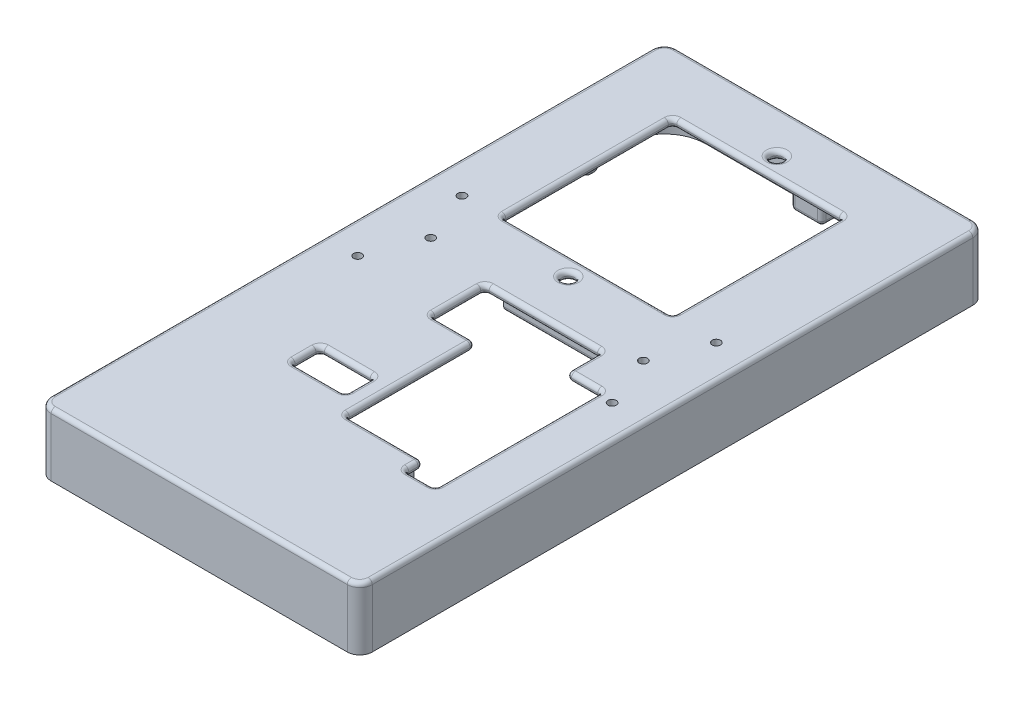
SolidWorks part; units mm, degrees
ref_plane "前视基准面" through (0, 0, 0) normal (0, 0, 1) x (1, 0, 0)
ref_plane "上视基准面" through (0, 0, 0) normal (0, 1, 0) x (1, 0, 0)
ref_plane "右视基准面" through (0, 0, 0) normal (1, 0, 0) x (0, 0, -1)
sketch "草图1" plane through (0, 0, 0) normal (0, 1, 0) x (1, 0, 0)
  line L0 (-212.3169, 718.1207) -> (-234.7066, 815.582) construction
  line L1 (-132.5632, 1387.3532) -> (-132.5632, 1244.1403) construction
  line L2 (-45.1474, 1386.0064) -> (-45.1474, 1242.0064)
  line L3 (-110.6474, 1387.5064) -> (-86.8035, 1387.5064)
  line L4 (-120.6474, 1377.5064) -> (-120.6474, 1369.0064)
  line L5 (-110.6474, 1240.5064) -> (-86.8035, 1240.5064)
  line L6 (-46.6474, 1377.5064) -> (-46.6474, 1369.0064)
  line L7 (-119.1474, 1239.0064) -> (-48.1474, 1239.0064)
  line L8 (-122.1474, 1386.0064) -> (-122.1474, 1242.0064)
  line L9 (-119.1474, 1389.0064) -> (-48.1474, 1389.0064)
  line L10 (-120.6474, 1240.5064) -> (-46.6474, 1240.5064) construction
  line L11 (-46.6474, 1387.5064) -> (-46.6474, 1240.5064) construction
  line L12 (-120.6474, 1387.5064) -> (-120.6474, 1240.5064) construction
  line L13 (-120.6474, 1387.5064) -> (-46.6474, 1387.5064) construction
  line L14 (-45.1474, 1389.0064) -> (-45.1474, 1239.0064) construction
  line L15 (-122.1474, 1239.0064) -> (-45.1474, 1239.0064) construction
  line L16 (-122.1474, 1389.0064) -> (-122.1474, 1239.0064) construction
  line L17 (-122.1474, 1389.0064) -> (-45.1474, 1389.0064) construction
  line L18 (-83.6474, 1387.5064) -> (-83.6474, 1240.5064) construction
  line L19 (-46.6474, 1369.0064) -> (-49.6474, 1369.0064)
  line L21 (-46.6474, 1366.0064) -> (-49.6474, 1366.0064)
  line L22 (-49.6474, 1369.0064) -> (-49.6474, 1366.0064)
  line L23 (-46.6474, 1314.0064) -> (-120.6474, 1314.0064) construction
  line L24 (-46.6474, 1366.0064) -> (-46.6474, 1262.0064)
  line L25 (-46.6474, 1259.0064) -> (-49.6474, 1259.0064)
  line L26 (-49.6474, 1259.0064) -> (-49.6474, 1262.0064)
  line L27 (-46.6474, 1262.0064) -> (-49.6474, 1262.0064)
  line L28 (-120.6474, 1369.0064) -> (-117.6474, 1369.0064)
  line L29 (-117.6474, 1369.0064) -> (-117.6474, 1366.0064)
  line L30 (-120.6474, 1366.0064) -> (-117.6474, 1366.0064)
  line L31 (-120.6474, 1262.0064) -> (-117.6474, 1262.0064)
  line L32 (-117.6474, 1259.0064) -> (-117.6474, 1262.0064)
  line L33 (-46.6474, 1259.0064) -> (-46.6474, 1250.5064)
  line L34 (-120.6474, 1366.0064) -> (-120.6474, 1262.0064)
  line L35 (-117.6474, 1259.0064) -> (-120.6474, 1259.0064)
  line L36 (-120.6474, 1259.0064) -> (-120.6474, 1250.5064)
  line L37 (-79.37, 1387.5064) -> (-56.6474, 1387.5064)
  line L39 (-79.37, 1387.5064) -> (-79.37, 1384.0064)
  line L40 (-79.37, 1384.0064) -> (-86.8035, 1384.0064)
  line L41 (-86.8035, 1387.5064) -> (-86.8035, 1384.0064)
  line L43 (-80.7882, 1240.5064) -> (-80.7882, 1243.5064)
  line L44 (-80.7882, 1243.5064) -> (-86.8035, 1243.5064)
  line L45 (-86.8035, 1240.5064) -> (-86.8035, 1243.5064)
  line L46 (-80.7882, 1240.5064) -> (-56.6474, 1240.5064)
  arc A0 (-56.6474, 1240.5064) -> (-46.6474, 1250.5064) centre (-56.6474, 1250.5064) ccw
  arc A1 (-120.6474, 1250.5064) -> (-110.6474, 1240.5064) centre (-110.6474, 1250.5064) ccw
  arc A2 (-110.6474, 1387.5064) -> (-120.6474, 1377.5064) centre (-110.6474, 1377.5064) ccw
  arc A3 (-56.6474, 1387.5064) -> (-46.6474, 1377.5064) centre (-56.6474, 1377.5064) cw
  arc A4 (-45.1474, 1242.0064) -> (-48.1474, 1239.0064) centre (-48.1474, 1242.0064) cw
  arc A5 (-119.1474, 1239.0064) -> (-122.1474, 1242.0064) centre (-119.1474, 1242.0064) cw
  arc A6 (-122.1474, 1386.0064) -> (-119.1474, 1389.0064) centre (-119.1474, 1386.0064) cw
  arc A7 (-45.1474, 1386.0064) -> (-48.1474, 1389.0064) centre (-48.1474, 1386.0064) ccw
  point P48 (-48.1474, 1259.0064)
  point P55 (-119.1474, 1259.0064)
  dimension "D3" = 10
  dimension "D4" = 3
  dimension "D1" = 100
  dimension "D5" = 3
  dimension "D6" = 20
  dimension "D7" = 3
  dimension "D8" = 71
  dimension "D9" = 144
  dimension "D10" = 3.5
  dimension "D11" = 3
  dimension "D2" = 1.5
extrude "凸台-拉伸1" add sketch "草图1" along normal blind 15
fillet "圆角1" radius 1 12 edges at (-117.6474, 7.5, -1259.0064) (-117.6474, 7.5, -1262.0064) (-49.6474, 7.5, -1259.0064) (-49.6474, 7.5, -1262.0064) (-49.6474, 7.5, -1366.0064) (-49.6474, 7.5, -1369.0064) (-117.6474, 7.5, -1366.0064) (-117.6474, 7.5, -1369.0064) (-86.8035, 7.5, -1243.5064) (-80.7882, 7.5, -1243.5064) (-79.37, 7.5, -1384.0064) (-86.8035, 7.5, -1384.0064)
sketch "草图2" plane through (0, 15, 0) normal (0, 1, 0) x (1, 0, 0)
  line L0 (-117.9843, 1353.593) -> (-118.8671, 1253.5969) construction
  line L1 (-65.1474, 1308.7566) -> (-65.1474, 1318.5064)
  line L2 (-66.1474, 1319.5064) -> (-92.1474, 1319.5064)
  line L3 (-93.1474, 1318.5064) -> (-93.1474, 1313.0064)
  line L4 (-45.1474, 1242.0064) -> (-45.1474, 1386.0064)
  line L5 (-48.1474, 1389.0064) -> (-119.1474, 1389.0064)
  line L6 (-122.1474, 1386.0064) -> (-122.1474, 1242.0064)
  line L7 (-119.1474, 1239.0064) -> (-48.1474, 1239.0064)
  line L8 (-45.1474, 1242.0064) -> (-45.1474, 1386.0064)
  line L9 (-48.1474, 1389.0064) -> (-119.1474, 1389.0064)
  line L10 (-122.1474, 1386.0064) -> (-122.1474, 1242.0064)
  line L11 (-119.1474, 1239.0064) -> (-48.1474, 1239.0064)
  line L12 (-94.1474, 1312.0064) -> (-95.1474, 1312.0064)
  line L13 (-96.1474, 1311.0064) -> (-96.1474, 1305.0064)
  line L14 (-95.1474, 1304.0064) -> (-86.1474, 1304.0064)
  line L15 (-85.1474, 1303.0064) -> (-85.1474, 1274.0064)
  line L16 (-84.1474, 1273.0064) -> (-65.1474, 1273.0064)
  line L17 (-89.1474, 1277.5064) -> (-99.1474, 1277.5064)
  line L18 (-100.1474, 1278.5064) -> (-100.1474, 1283.5064)
  line L19 (-99.1474, 1284.5064) -> (-89.1474, 1284.5064)
  line L20 (-88.1474, 1283.5064) -> (-88.1474, 1278.5064)
  line L21 (-84.6474, 1378.5064) -> (-84.6474, 1328.5064) construction
  line L22 (-104.1474, 1374.0064) -> (-65.1474, 1374.0064)
  line L23 (-105.1474, 1373.0064) -> (-105.1474, 1334.0064)
  line L24 (-104.1474, 1333.0064) -> (-65.1474, 1333.0064)
  line L25 (-64.1474, 1373.0064) -> (-64.1474, 1334.0064)
  line L26 (-65.1474, 1273.0064) -> (-64.1474, 1273.0064)
  line L27 (-65.1474, 1308.7566) -> (-55.8177, 1308.7566)
  line L28 (-64.1474, 1273.0064) -> (-64.1474, 1269.7566)
  line L29 (-63.1474, 1268.7566) -> (-56.8177, 1268.7566)
  line L30 (-55.8177, 1308.7566) -> (-55.8177, 1269.7566)
  arc A0 (-65.1474, 1318.5064) -> (-66.1474, 1319.5064) centre (-66.1474, 1318.5064) ccw
  arc A2 (-85.1474, 1274.0064) -> (-84.1474, 1273.0064) centre (-84.1474, 1274.0064) ccw
  arc A3 (-86.1474, 1304.0064) -> (-85.1474, 1303.0064) centre (-86.1474, 1303.0064) cw
  arc A4 (-48.1474, 1239.0064) -> (-45.1474, 1242.0064) centre (-48.1474, 1242.0064) ccw
  arc A5 (-45.1474, 1386.0064) -> (-48.1474, 1389.0064) centre (-48.1474, 1386.0064) ccw
  arc A6 (-119.1474, 1389.0064) -> (-122.1474, 1386.0064) centre (-119.1474, 1386.0064) ccw
  arc A7 (-122.1474, 1242.0064) -> (-119.1474, 1239.0064) centre (-119.1474, 1242.0064) ccw
  arc A8 (-48.1474, 1239.0064) -> (-45.1474, 1242.0064) centre (-48.1474, 1242.0064) ccw
  arc A9 (-45.1474, 1386.0064) -> (-48.1474, 1389.0064) centre (-48.1474, 1386.0064) ccw
  arc A10 (-119.1474, 1389.0064) -> (-122.1474, 1386.0064) centre (-119.1474, 1386.0064) ccw
  arc A11 (-122.1474, 1242.0064) -> (-119.1474, 1239.0064) centre (-119.1474, 1242.0064) ccw
  arc A12 (-92.1474, 1319.5064) -> (-93.1474, 1318.5064) centre (-92.1474, 1318.5064) ccw
  arc A13 (-93.1474, 1313.0064) -> (-94.1474, 1312.0064) centre (-94.1474, 1313.0064) cw
  arc A14 (-95.1474, 1312.0064) -> (-96.1474, 1311.0064) centre (-95.1474, 1311.0064) ccw
  arc A15 (-96.1474, 1305.0064) -> (-95.1474, 1304.0064) centre (-95.1474, 1305.0064) ccw
  arc A16 (-89.1474, 1284.5064) -> (-88.1474, 1283.5064) centre (-89.1474, 1283.5064) cw
  arc A17 (-89.1474, 1277.5064) -> (-88.1474, 1278.5064) centre (-89.1474, 1278.5064) ccw
  arc A18 (-99.1474, 1277.5064) -> (-100.1474, 1278.5064) centre (-99.1474, 1278.5064) cw
  arc A19 (-100.1474, 1283.5064) -> (-99.1474, 1284.5064) centre (-99.1474, 1283.5064) cw
  arc A20 (-65.1474, 1333.0064) -> (-64.1474, 1334.0064) centre (-65.1474, 1334.0064) ccw
  arc A21 (-105.1474, 1334.0064) -> (-104.1474, 1333.0064) centre (-104.1474, 1334.0064) ccw
  arc A22 (-104.1474, 1374.0064) -> (-105.1474, 1373.0064) centre (-104.1474, 1373.0064) ccw
  arc A23 (-65.1474, 1374.0064) -> (-64.1474, 1373.0064) centre (-65.1474, 1373.0064) cw
  circle A24 centre (-84.6474, 1378.5064) radius 1.5
  circle A25 centre (-84.6474, 1328.5064) radius 1.5
  arc A26 (-64.1474, 1269.7566) -> (-63.1474, 1268.7566) centre (-63.1474, 1269.7566) ccw
  arc A27 (-56.8177, 1268.7566) -> (-55.8177, 1269.7566) centre (-56.8177, 1269.7566) ccw
  point P28 (-65.1474, 1319.5064)
  point P31 (-65.1474, 1273.0064)
  point P34 (-85.1474, 1273.0064)
  point P37 (-85.1474, 1304.0064)
  point P40 (-93.1474, 1319.5064)
  point P43 (-93.1474, 1312.0064)
  point P46 (-96.1474, 1312.0064)
  point P49 (-96.1474, 1304.0064)
  point P52 (-88.1474, 1284.5064)
  point P55 (-88.1474, 1277.5064)
  point P58 (-100.1474, 1277.5064)
  point P69 (-105.1474, 1333.0064)
  point P72 (-105.1474, 1374.0064)
  point P75 (-64.1474, 1374.0064)
  point P78 (-84.6474, 1353.5064)
  point P79 (-64.1474, 1353.5064)
  dimension "D15" = 1
  dimension "D20" = 1
  dimension "D22" = 34
  dimension "D23" = 1
  dimension "D2" = 100
  dimension "D3" = 20
  dimension "D4" = 28
  dimension "D5" = 7.5
  dimension "D6" = 8
  dimension "D7" = 11
  dimension "D8" = 3
  dimension "D9" = 31
  dimension "D10" = 39
  dimension "D11" = 46.5
  dimension "D12" = 22
  dimension "D13" = 12
  dimension "D14" = 7
  dimension "D16" = 19
  dimension "D17" = 15
  dimension "D18" = 41
  dimension "D19" = 41
  dimension "D21" = 50
  dimension "D24" = 38.5
  dimension "D1" = 0
extrude "凸台-拉伸2" add sketch "草图2" against normal blind 2
sketch "草图6" plane through (0, 15, 0) normal (0, 1, 0) x (1, 0, 0)
  line L0 (-93.1474, 1313.0064) -> (-93.1474, 1304.0064)
  line L1 (-95.1474, 1304.0064) -> (-86.1474, 1304.0064) construction
  line L2 (-93.1474, 1304.0064) -> (-97.2959, 1304.0064)
  line L3 (-97.2959, 1304.0064) -> (-97.2959, 1313.0064)
  line L4 (-97.2959, 1313.0064) -> (-93.1474, 1313.0064)
  line L5 (-56.8177, 1268.7566) -> (-56.8177, 1308.7566)
  line L6 (-55.8177, 1308.7566) -> (-65.1474, 1308.7566) construction
  line L7 (-56.8177, 1308.7566) -> (-55.8177, 1308.7566)
  line L8 (-55.8177, 1308.7566) -> (-55.8177, 1268.7566)
  line L9 (-55.8177, 1268.7566) -> (-56.8177, 1268.7566)
  line L10 (-93.1474, 1317.0064) -> (-65.1474, 1317.0064)
  line L11 (-93.1474, 1318.5064) -> (-93.1474, 1313.0064) construction
  line L12 (-65.1474, 1308.7566) -> (-65.1474, 1318.5064) construction
  line L13 (-66.1474, 1319.5064) -> (-92.1474, 1319.5064) construction
  line L14 (-93.1474, 1317.0064) -> (-93.1474, 1319.5064)
  line L15 (-93.1474, 1319.5064) -> (-65.1474, 1319.5064)
  line L16 (-65.1474, 1319.5064) -> (-65.1474, 1317.0064)
  line L17 (-82.6474, 1273.0064) -> (-82.6474, 1304.0064)
  line L18 (-84.1474, 1273.0064) -> (-64.1474, 1273.0064) construction
  line L19 (-82.6474, 1304.0064) -> (-86.6707, 1304.0064)
  line L20 (-85.1474, 1303.0064) -> (-85.1474, 1274.0064) construction
  line L21 (-82.6474, 1273.0064) -> (-86.6707, 1273.0064)
  line L22 (-86.6707, 1273.0064) -> (-86.6707, 1304.0064)
  dimension "D1" = 2.5
  dimension "D2" = 2.5
extrude "凸台-拉伸4" add sketch "草图6" against normal up to surface (2 mm away) up to face at (-83.5912, 13, -1313.9609)
fillet "圆角7" radius 1 9 edges at (-93.1474, 14, -1317.0064) (-93.1474, 14, -1304.0064) (-82.6474, 14, -1304.0064) (-82.6474, 14, -1273.0064) (-64.1474, 14, -1273.0064) (-56.8177, 14, -1268.7566) (-56.8177, 14, -1308.7566) (-65.1474, 14, -1308.7566) (-65.1474, 14, -1317.0064)
sketch "草图7" plane through (0, 15, 0) normal (0, 1, 0) x (1, 0, 0)
  line L0 (-89.1474, 1284.5064) -> (-88.1474, 1284.5064)
  line L1 (-87.1474, 1283.5064) -> (-87.1474, 1278.5064)
  line L2 (-88.1474, 1277.5064) -> (-89.1474, 1277.5064)
  line L3 (-89.1474, 1277.5064) -> (-89.1474, 1284.5064)
  arc A0 (-87.1474, 1278.5064) -> (-88.1474, 1277.5064) centre (-88.1474, 1278.5064) cw
  arc A1 (-88.1474, 1284.5064) -> (-87.1474, 1283.5064) centre (-88.1474, 1283.5064) cw
  dimension "D1" = 1
extrude "切除-拉伸3" cut sketch "草图7" against normal up to surface (2 mm away) up to face at (-72.3815, 13, -1294.3064)
sketch "草图8" plane through (0, 13, 0) normal (0, -1, 0) x (1, 0, 0)
  line L0 (-46.6474, -1314.0064) -> (-120.6474, -1314.0064) construction
  line L1 (-46.6474, -1262.0064) -> (-46.6474, -1366.0064) construction
  line L2 (-120.6474, -1366.0064) -> (-120.6474, -1262.0064) construction
  line L3 (-48.6474, -1369.0064) -> (-46.6474, -1369.0064) construction
  line L4 (-49.6474, -1367.0064) -> (-49.6474, -1368.0064) construction
  line L5 (-46.6474, -1366.0064) -> (-48.6474, -1366.0064) construction
  line L6 (-48.6474, -1369.0064) -> (-46.6474, -1369.0064) construction
  line L7 (-49.6474, -1367.0064) -> (-49.6474, -1368.0064) construction
  line L8 (-46.6474, -1366.0064) -> (-48.6474, -1366.0064) construction
  line L9 (-48.6474, -1315.5064) -> (-46.6474, -1315.5064)
  line L10 (-49.6474, -1313.5064) -> (-49.6474, -1314.5064)
  line L11 (-46.6474, -1312.5064) -> (-48.6474, -1312.5064)
  line L12 (-83.6474, -1389.0064) -> (-83.6474, -1239.0064) construction
  line L13 (-48.1474, -1389.0064) -> (-119.1474, -1389.0064) construction
  line L14 (-119.1474, -1239.0064) -> (-48.1474, -1239.0064) construction
  line L15 (-120.6474, -1312.5064) -> (-118.6474, -1312.5064)
  line L16 (-117.6474, -1313.5064) -> (-117.6474, -1314.5064)
  line L17 (-118.6474, -1315.5064) -> (-120.6474, -1315.5064)
  line L18 (-46.6474, -1315.5064) -> (-46.6474, -1312.5064)
  line L19 (-120.6474, -1315.5064) -> (-120.6474, -1312.5064)
  arc A0 (-49.6474, -1368.0064) -> (-48.6474, -1369.0064) centre (-48.6474, -1368.0064) ccw construction
  arc A1 (-48.6474, -1366.0064) -> (-49.6474, -1367.0064) centre (-48.6474, -1367.0064) ccw construction
  arc A2 (-49.6474, -1368.0064) -> (-48.6474, -1369.0064) centre (-48.6474, -1368.0064) ccw construction
  arc A3 (-48.6474, -1366.0064) -> (-49.6474, -1367.0064) centre (-48.6474, -1367.0064) ccw construction
  arc A4 (-49.6474, -1314.5064) -> (-48.6474, -1315.5064) centre (-48.6474, -1314.5064) ccw
  arc A5 (-48.6474, -1312.5064) -> (-49.6474, -1313.5064) centre (-48.6474, -1313.5064) ccw
  arc A6 (-118.6474, -1312.5064) -> (-117.6474, -1313.5064) centre (-118.6474, -1313.5064) cw
  arc A7 (-117.6474, -1314.5064) -> (-118.6474, -1315.5064) centre (-118.6474, -1314.5064) cw
  dimension "D1" = 2
extrude "凸台-拉伸5" add sketch "草图8" along normal up to surface (13 mm away) up to face at (-83.6474, 0, -1314.0064)
fillet "圆角2" radius 1 46 edges at (-93.1474, 15, -1310.5064) (-87.8974, 15, -1304.0064) (-73.3974, 15, -1273.0064) (-65.1474, 15, -1312.8815) (-93.6474, 15, -1284.5064) (-99.8545, 15, -1284.2135) (-100.1474, 15, -1281.0064) (-99.8545, 15, -1277.7993) (-93.6474, 15, -1277.5064) (-83.6474, 15, -1239.0064) (-121.2687, 15, -1239.885) (-122.1474, 15, -1314.0064) (-121.2687, 15, -1388.1277) (-83.6474, 15, -1389.0064) (-46.0261, 15, -1388.1277) (-45.1474, 15, -1314.0064) (-46.0261, 15, -1239.885) (-64.1474, 15, -1353.5064) (-64.4403, 15, -1373.7135) (-84.6474, 15, -1374.0064) (-104.8545, 15, -1373.7135) (-105.1474, 15, -1353.5064) (-104.8545, 15, -1333.2993) (-84.6474, 15, -1333.0064) (-64.4403, 15, -1333.2993) (-84.6474, 15, -1377.0064) (-84.6474, 15, -1327.0064) (-60.4826, 15, -1268.7566) (-60.9826, 15, -1308.7566) (-64.1474, 15, -1270.8815) (-63.8545, 15, -1269.0495) (-56.8177, 15, -1288.7566) (-79.1474, 15, -1317.0064) (-82.6474, 15, -1288.5064) (-87.4403, 15, -1277.7993) (-87.1474, 15, -1281.0064) (-87.4403, 15, -1284.2135) (-82.3545, 15, -1273.2993) (-64.4403, 15, -1272.7135) (-57.1106, 15, -1269.0495) (-57.1106, 15, -1308.4637) (-64.8545, 15, -1309.0495) (-65.4403, 15, -1316.7135) (-92.8545, 15, -1316.7135) (-92.8545, 15, -1304.2993) (-82.9403, 15, -1303.7135)
fillet "圆角3" radius 1 25 edges at (-49.3545, 0, -1261.7135) (-47.6474, 0, -1262.0064) (-49.6474, 0, -1260.5064) (-49.3545, 0, -1259.2993) (-47.6474, 0, -1259.0064) (-119.6474, 0, -1262.0064) (-117.9403, 0, -1261.7135) (-117.6474, 0, -1260.5064) (-117.9403, 0, -1259.2993) (-119.6474, 0, -1369.0064) (-117.9403, 0, -1368.7135) (-117.6474, 0, -1367.5064) (-117.9403, 0, -1366.2993) (-86.8035, 0, -1386.2564) (-86.5106, 0, -1384.2993) (-83.0867, 0, -1384.0064) (-79.6629, 0, -1384.2993) (-47.6474, 0, -1369.0064) (-49.3545, 0, -1368.7135) (-49.6474, 0, -1367.5064) (-49.3545, 0, -1366.2993) (-119.6474, 0, -1259.0064) (-119.6474, 0, -1366.0064) (-79.37, 0, -1386.2564) (-47.6474, 0, -1366.0064)
fillet "圆角4" radius 1 94 edges at (-73.3974, 13, -1273.0064) (-87.8974, 13, -1304.0064) (-93.1474, 13, -1310.5064) (-65.1474, 13, -1312.8815) (-93.6474, 13, -1277.5064) (-99.8545, 13, -1277.7993) (-100.1474, 13, -1281.0064) (-99.8545, 13, -1284.2135) (-93.6474, 13, -1284.5064) (-86.5106, 13, -1243.2135) (-83.7958, 13, -1243.5064) (-81.0811, 13, -1243.2135) (-80.7882, 13, -1241.5064) (-68.7178, 13, -1240.5064) (-49.5764, 13, -1243.4353) (-46.6474, 13, -1254.7564) (-47.6474, 13, -1259.0064) (-49.3545, 13, -1259.2993) (-49.6474, 13, -1260.5064) (-49.3545, 13, -1261.7135) (-47.6474, 13, -1262.0064) (-46.6474, 13, -1340.7564) (-46.6474, 13, -1287.2564) (-47.6474, 13, -1366.0064) (-49.3545, 13, -1366.2993) (-49.6474, 13, -1367.5064) (-49.3545, 13, -1368.7135) (-47.6474, 13, -1369.0064) (-46.6474, 13, -1373.2564) (-49.5764, 13, -1384.5774) (-68.0087, 13, -1387.5064) (-79.37, 13, -1386.2564) (-79.6629, 13, -1384.2993) (-83.0867, 13, -1384.0064) (-86.5106, 13, -1384.2993) (-86.8035, 13, -1386.2564) (-98.7254, 13, -1387.5064) (-117.7185, 13, -1384.5774) (-120.6474, 13, -1373.2564) (-119.6474, 13, -1369.0064) (-117.9403, 13, -1368.7135) (-117.6474, 13, -1367.5064) (-117.9403, 13, -1366.2993) (-119.6474, 13, -1366.0064) (-120.6474, 13, -1340.7564) (-120.6474, 13, -1287.2564) (-119.6474, 13, -1262.0064) (-117.9403, 13, -1261.7135) (-117.6474, 13, -1260.5064) (-117.9403, 13, -1259.2993) (-119.6474, 13, -1259.0064) (-120.6474, 13, -1254.7564) (-117.7185, 13, -1243.4353) (-98.7254, 13, -1240.5064) (-86.8035, 13, -1241.5064) (-104.8545, 13, -1333.2993) (-105.1474, 13, -1353.5064) (-104.8545, 13, -1373.7135) (-84.6474, 13, -1374.0064) (-64.4403, 13, -1373.7135) (-64.1474, 13, -1353.5064) (-64.4403, 13, -1333.2993) (-84.6474, 13, -1333.0064) (-84.6474, 13, -1377.0064) (-84.6474, 13, -1327.0064) (-60.9826, 13, -1308.7566) (-60.4826, 13, -1268.7566) (-63.8545, 13, -1269.0495) (-64.1474, 13, -1270.8815) (-82.6474, 13, -1288.5064) (-79.1474, 13, -1317.0064) (-56.8177, 13, -1288.7566) (-87.1474, 13, -1281.0064) (-87.4403, 13, -1277.7993) (-87.4403, 13, -1284.2135) (-92.8545, 13, -1304.2993) (-92.8545, 13, -1316.7135) (-65.4403, 13, -1316.7135) (-64.8545, 13, -1309.0495) (-57.1106, 13, -1308.4637) (-57.1106, 13, -1269.0495) (-64.4403, 13, -1272.7135) (-82.3545, 13, -1273.2993) (-82.9403, 13, -1303.7135) (-47.6474, 13, -1312.5064) (-49.3545, 13, -1312.7993) (-49.6474, 13, -1314.0064) (-49.3545, 13, -1315.2135) (-47.6474, 13, -1315.5064) (-119.6474, 13, -1315.5064) (-117.9403, 13, -1315.2135) (-117.6474, 13, -1314.0064) (-117.9403, 13, -1312.7993) (-119.6474, 13, -1312.5064)
sketch "草图3" plane through (0, 0, 0) normal (0, -1, 0) x (1, 0, 0)
  line L0 (-119.1474, -1239.0064) -> (-48.1474, -1239.0064) construction
  line L2 (-45.1474, -1242.0064) -> (-45.1474, -1386.0064) construction
  line L3 (-45.1474, -1314.0064) -> (-122.1474, -1314.0064) construction
  line L4 (-122.1474, -1386.0064) -> (-122.1474, -1242.0064) construction
  line L5 (-83.6474, -1314.0064) -> (-83.6474, -1389.0064) construction
  line L6 (-48.1474, -1389.0064) -> (-119.1474, -1389.0064) construction
  circle A0 centre (-47.6474, -1241.5064) radius 0.95
  circle A1 centre (-47.6474, -1386.5064) radius 0.95
  circle A2 centre (-119.6474, -1386.5064) radius 0.95
  circle A3 centre (-119.6474, -1241.5064) radius 0.95
  dimension "D2" = 1.9
  dimension "D3" = 2.5
  dimension "D1" = 2.5
extrude "切除-拉伸1" cut sketch "草图3" against normal blind 10
sketch "草图4" plane through (0, 13, 0) normal (0, -1, 0) x (1, 0, 0)
  line L5 (-65.1474, -1272.0064) -> (-84.1897, -1272.0064)
  line L6 (-65.1474, -1272.0064) -> (-65.1474, -1269.3636)
  line L7 (-92.1474, -1320.5064) -> (-66.0382, -1320.5064)
  line L8 (-92.1474, -1320.5064) -> (-92.1474, -1323.5064)
  line L9 (-91.1474, -1324.5064) -> (-67.0382, -1324.5064)
  line L10 (-66.0382, -1320.5064) -> (-66.0382, -1323.5064)
  line L11 (-65.1474, -1269.3636) -> (-83.1897, -1269.3636)
  line L12 (-84.1897, -1272.0064) -> (-84.1897, -1270.3636)
  line L13 (-108.4861, -1336.7616) -> (-111.7983, -1336.7616)
  line L14 (-107.4861, -1335.7616) -> (-107.4861, -1333.7616)
  line L15 (-108.4861, -1332.7616) -> (-111.7983, -1332.7616)
  line L16 (-112.7983, -1335.7616) -> (-112.7983, -1333.7616)
  arc A4 (-92.1474, -1323.5064) -> (-91.1474, -1324.5064) centre (-91.1474, -1323.5064) ccw
  arc A5 (-67.0382, -1324.5064) -> (-66.0382, -1323.5064) centre (-67.0382, -1323.5064) ccw
  arc A6 (-83.1897, -1269.3636) -> (-84.1897, -1270.3636) centre (-83.1897, -1270.3636) ccw
  arc A7 (-111.7983, -1332.7616) -> (-112.7983, -1333.7616) centre (-111.7983, -1333.7616) ccw
  arc A8 (-111.7983, -1336.7616) -> (-112.7983, -1335.7616) centre (-111.7983, -1335.7616) cw
  arc A9 (-108.4861, -1336.7616) -> (-107.4861, -1335.7616) centre (-108.4861, -1335.7616) ccw
  arc A10 (-107.4861, -1333.7616) -> (-108.4861, -1332.7616) centre (-108.4861, -1333.7616) ccw
  point P28 (-66.0382, -1324.5064)
  dimension "D7" = 1
  dimension "D1" = 1
  dimension "D2" = 1
  dimension "D6" = 4
extrude "凸台-拉伸3" add sketch "草图4" along normal blind 5
fillet "圆角6" radius 1 6 edges at (-79.0928, 8, -1320.5064) (-66.0382, 8, -1322.0064) (-66.3311, 8, -1324.2135) (-79.0928, 8, -1324.5064) (-91.8545, 8, -1324.2135) (-92.1474, 8, -1322.0064)
sketch "草图5" plane through (0, 15, 0) normal (0, 1, 0) x (1, 0, 0)
  line L0 (-53.1474, 1307.5064) -> (-53.1474, 1332.5064) construction
  line L1 (-45.1474, 1386.0064) -> (-45.1474, 1242.0064) construction
  line L2 (-53.1474, 1320.0064) -> (-58.1474, 1320.0064) construction
  line L3 (-83.6474, 1240.0064) -> (-83.6474, 1388.0064) construction
  line L4 (-119.1474, 1240.0064) -> (-48.1474, 1240.0064) construction
  line L5 (-48.1474, 1388.0064) -> (-119.1474, 1388.0064) construction
  line L6 (-114.1474, 1320.0064) -> (-109.1474, 1320.0064) construction
  line L7 (-114.1474, 1307.5064) -> (-114.1474, 1332.5064) construction
  circle A0 centre (-58.1474, 1320.0064) radius 1
  circle A1 centre (-53.1474, 1307.5064) radius 1
  circle A2 centre (-53.1474, 1332.5064) radius 1
  circle A3 centre (-114.1474, 1332.5064) radius 1
  circle A4 centre (-114.1474, 1307.5064) radius 1
  circle A5 centre (-109.1474, 1320.0064) radius 1
  dimension "D4" = 80
  dimension "D1" = 8
  dimension "D2" = 25
  dimension "D3" = 5
extrude "切除-拉伸2" cut sketch "草图5" against normal up to surface (2 mm away) up to face at (-110.1422, 13, -1334.7616)
sketch "草图9" plane through (0, 0, 0) normal (0, -1, 0) x (1, 0, 0)
  line L0 (-45.1474, -1242.0064) -> (-45.1474, -1386.0064) construction
  line L1 (-83.6474, -1389.0064) -> (-83.6474, -1239.0064) construction
  line L2 (-48.1474, -1389.0064) -> (-119.1474, -1389.0064) construction
  line L3 (-119.1474, -1239.0064) -> (-48.1474, -1239.0064) construction
  circle A0 centre (-47.1474, -1314.0319) radius 0.675
  circle A1 centre (-120.1474, -1314.0319) radius 0.675
  dimension "D1" = 1.35
  dimension "D2" = 2
extrude "切除-拉伸4" cut sketch "草图9" against normal blind 10
fillet "圆角8" radius 1 8 edges at (-120.3545, 12.7071, -1315.7993) (-120.3545, 12.7071, -1312.2135) (-46.9403, 12.7071, -1315.7993) (-46.9403, 12.7071, -1312.2135) (-120.6474, 6, -1315.5064) (-120.6474, 6, -1312.5064) (-46.6474, 6, -1315.5064) (-46.6474, 6, -1312.5064)
